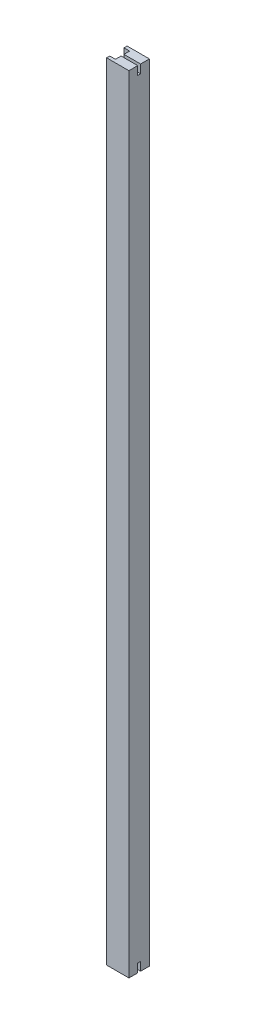
SolidWorks part; units mm, degrees
ref_plane "Спереди" through (0, 0, 0) normal (0, 0, 1) x (1, 0, 0)
ref_plane "Сверху" through (0, 0, 0) normal (0, 1, 0) x (1, 0, 0)
ref_plane "Справа" through (0, 0, 0) normal (1, 0, 0) x (0, 0, -1)
sketch "Эскиз1" plane through (0, 0, 0) normal (0, 1, 0) x (1, 0, 0)
  line L1 (10, 2.5) -> (10, 12.5)
  line L2 (10, 12.5) -> (0, 12.5)
  line L3 (0, 12.5) -> (0, 18)
  line L4 (0, 18) -> (39.2552, 18)
  line L5 (39.2552, 18) -> (39.2552, -18)
  line L7 (10, 2.5) -> (0, 2.5)
  line L8 (0, 2.5) -> (0, -2.5)
  line L9 (-20.2057, 0) -> (49.5465, 0) construction
  line L10 (10, -2.5) -> (0, -2.5)
  line L11 (0, -18) -> (39.2552, -18)
  line L12 (0, -12.5) -> (0, -18)
  line L13 (10, -12.5) -> (0, -12.5)
  line L14 (10, -2.5) -> (10, -12.5)
  point P12 (0, 0)
  point P14 (39.2552, 0)
  point P17 (0, 0)
  point P18 (0, 0)
  point P19 (0, 0)
  point P20 (0, 0)
extrude "Бобышка-Вытянуть1" add sketch "Эскиз1" along normal blind 1383.55
sketch "Эскиз3" plane through (39.2552, 0, 0) normal (1, 0, 0) x (0, 0, -1)
  line L0 (2.5, 0) -> (-2.5, 0)
  line L1 (-18, 0) -> (18, 0) construction
  line L2 (-2.5, 0) -> (-2.5, 15)
  line L3 (-2.5, 15) -> (2.5, 15)
  line L4 (0, -5.4444) -> (0, 1435.7196) construction
  line L5 (2.5, 0) -> (2.5, 15)
  line L6 (44.6402, 691.775) -> (-39.1393, 691.775) construction
  line L7 (2.5, 1383.55) -> (2.5, 1368.55)
  line L8 (-2.5, 1368.55) -> (2.5, 1368.55)
  line L9 (-2.5, 1383.55) -> (-2.5, 1368.55)
  line L10 (2.5, 1383.55) -> (-2.5, 1383.55)
  line L11 (18, 1383.55) -> (18, 0) construction
  point P10 (0, 15)
  point P11 (0, 0)
  point P19 (18, 691.775)
  point P20 (-2.5, 1435.7196)
extrude "Вырез-Вытянуть4" cut sketch "Эскиз3" against normal through all
